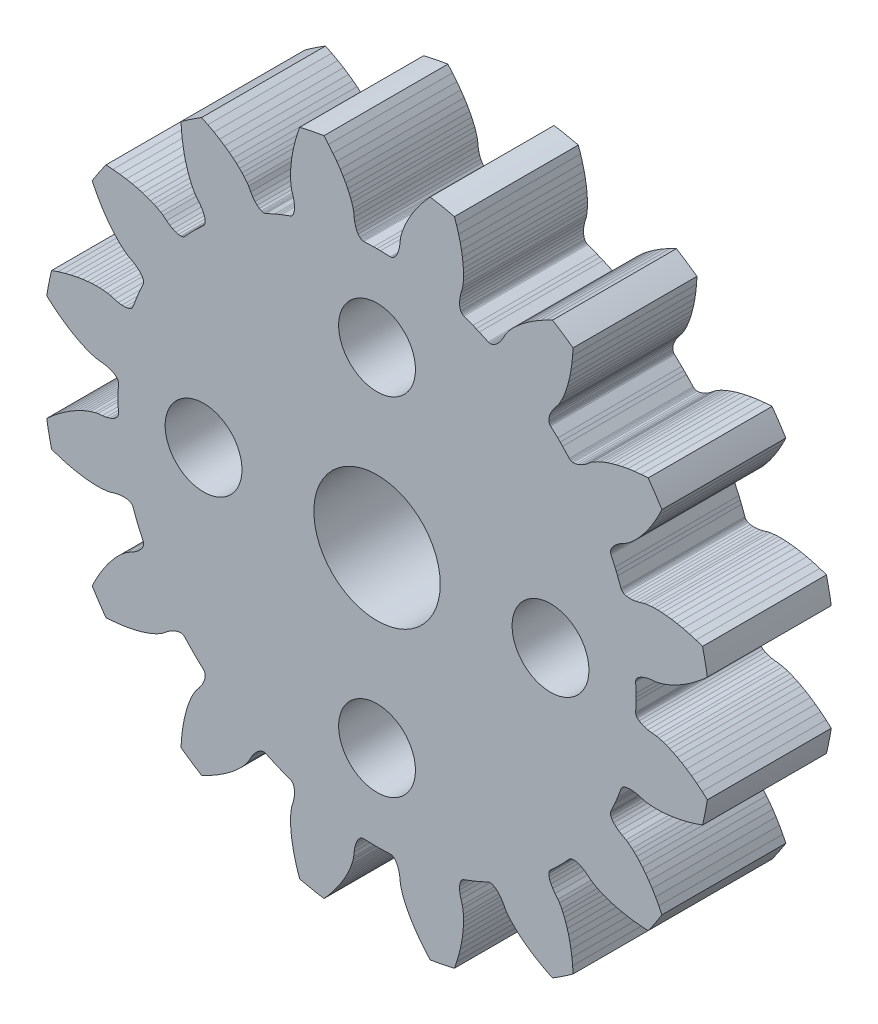
SolidWorks part; units mm, degrees
ref_plane "Płaszczyzna przednia" through (0, 0, 0) normal (0, 0, 1) x (1, 0, 0)
ref_plane "Płaszczyzna górna" through (0, 0, 0) normal (0, 1, 0) x (1, 0, 0)
ref_plane "Płaszczyzna prawa" through (0, 0, 0) normal (1, 0, 0) x (0, 0, -1)
sketch "szkic" plane through (0, 0, 0) normal (0, 0, 1) x (1, 0, 0)
  line L0 (-11.3707, -6.8275) -> (-11.2363, -6.5793)
  line L1 (-11.2363, -6.5793) -> (-11.1018, -6.3541)
  line L2 (-11.1018, -6.3541) -> (-10.9682, -6.1502)
  line L3 (-10.9682, -6.1502) -> (-10.8384, -5.969)
  line L4 (-10.8384, -5.969) -> (-10.7123, -5.8079)
  line L5 (-10.7123, -5.8079) -> (-10.5942, -5.6692)
  line L6 (-10.5942, -5.6692) -> (-10.4825, -5.5487)
  line L7 (-10.4825, -5.5487) -> (-10.3808, -5.4477)
  line L8 (-10.3808, -5.4477) -> (-10.2894, -5.3643)
  line L9 (-10.2894, -5.3643) -> (-10.1409, -5.2443)
  line L10 (-10.1409, -5.2443) -> (-10.0492, -5.182)
  line L11 (-10.0492, -5.182) -> (-9.889, -5.098)
  line L12 (-9.889, -5.098) -> (-9.7507, -5.012)
  line L13 (-9.7507, -5.012) -> (-9.6368, -4.9243)
  line L14 (-9.6368, -4.9243) -> (-9.5471, -4.8366)
  line L15 (-9.5471, -4.8366) -> (-9.4815, -4.751)
  line L16 (-9.4815, -4.751) -> (-9.4395, -4.6692)
  line L17 (-9.4395, -4.6692) -> (-9.4273, -4.6302)
  line L18 (-9.4273, -4.6302) -> (-9.4208, -4.593)
  line L19 (-9.4208, -4.593) -> (-9.4199, -4.5576)
  line L20 (-9.4199, -4.5576) -> (-9.4246, -4.5243)
  line L21 (-9.4246, -4.5243) -> (-9.4382, -4.4859)
  line L22 (-9.4382, -4.4859) -> (-9.6012, -4.1255)
  line L23 (-9.6012, -4.1255) -> (-9.6545, -3.999)
  line L24 (-9.6545, -3.999) -> (-9.7063, -3.8719)
  line L25 (-9.7063, -3.8719) -> (-9.8458, -3.5018)
  line L26 (-9.8458, -3.5018) -> (-9.8633, -3.4651)
  line L27 (-9.8633, -3.4651) -> (-9.8836, -3.4382)
  line L28 (-9.8836, -3.4382) -> (-9.9092, -3.4137)
  line L29 (-9.9092, -3.4137) -> (-9.9402, -3.392)
  line L30 (-9.9402, -3.392) -> (-9.9763, -3.3732)
  line L31 (-9.9763, -3.3732) -> (-10.0639, -3.345)
  line L32 (-10.0639, -3.345) -> (-10.1708, -3.3308)
  line L33 (-10.1708, -3.3308) -> (-10.2962, -3.3322)
  line L34 (-10.2962, -3.3322) -> (-10.4388, -3.3508)
  line L35 (-10.4388, -3.3508) -> (-10.5974, -3.3878)
  line L36 (-10.5974, -3.3878) -> (-10.7701, -3.4416)
  line L37 (-10.7701, -3.4416) -> (-10.879, -3.4624)
  line L38 (-10.879, -3.4624) -> (-11.0688, -3.4826)
  line L39 (-11.0688, -3.4826) -> (-11.1924, -3.4882)
  line L40 (-11.1924, -3.4882) -> (-11.3358, -3.4887)
  line L41 (-11.3358, -3.4887) -> (-11.4999, -3.4825)
  line L42 (-11.4999, -3.4825) -> (-11.6816, -3.468)
  line L43 (-11.6816, -3.468) -> (-11.8846, -3.4432)
  line L44 (-11.8846, -3.4432) -> (-12.1046, -3.4069)
  line L45 (-12.1046, -3.4069) -> (-12.3432, -3.3572)
  line L46 (-12.3432, -3.3572) -> (-12.5975, -3.293)
  line L47 (-12.5975, -3.293) -> (-12.868, -3.2125)
  line L48 (-12.868, -3.2125) -> (-13.1342, -3.1213)
  line L49 (-13.3289, -2.1426) -> (-13.1179, -1.9564)
  line L50 (-13.1179, -1.9564) -> (-12.8987, -1.7785)
  line L51 (-12.8987, -1.7785) -> (-12.6884, -1.6219)
  line L52 (-12.6884, -1.6219) -> (-12.4869, -1.4847)
  line L53 (-12.4869, -1.4847) -> (-12.2976, -1.367)
  line L54 (-12.2976, -1.367) -> (-12.1195, -1.2664)
  line L55 (-12.1195, -1.2664) -> (-11.9572, -1.1834)
  line L56 (-11.9572, -1.1834) -> (-11.808, -1.1149)
  line L57 (-11.808, -1.1149) -> (-11.6753, -1.0605)
  line L58 (-11.6753, -1.0605) -> (-11.5589, -1.0184)
  line L59 (-11.5589, -1.0184) -> (-11.3759, -0.9644)
  line L60 (-11.3759, -0.9644) -> (-11.2673, -0.9419)
  line L61 (-11.2673, -0.9419) -> (-11.0872, -0.9256)
  line L62 (-11.0872, -0.9256) -> (-10.9265, -0.8991)
  line L63 (-10.9265, -0.8991) -> (-10.7876, -0.8616)
  line L64 (-10.7876, -0.8616) -> (-10.6713, -0.8149)
  line L65 (-10.6713, -0.8149) -> (-10.5779, -0.7609)
  line L66 (-10.5779, -0.7609) -> (-10.5078, -0.7014)
  line L67 (-10.5078, -0.7014) -> (-10.4816, -0.6701)
  line L68 (-10.4816, -0.6701) -> (-10.4613, -0.6382)
  line L69 (-10.4613, -0.6382) -> (-10.447, -0.6058)
  line L70 (-10.447, -0.6058) -> (-10.4386, -0.5732)
  line L71 (-10.4386, -0.5732) -> (-10.4364, -0.5326)
  line L72 (-10.4364, -0.5326) -> (-10.4491, -0.1373)
  line L73 (-10.4491, -0.1373) -> (-10.45, 0)
  line L74 (-10.45, 0) -> (-10.4491, 0.1373)
  line L75 (-10.4491, 0.1373) -> (-10.4364, 0.5326)
  line L76 (-10.4364, 0.5326) -> (-10.4386, 0.5732)
  line L77 (-10.4386, 0.5732) -> (-10.447, 0.6058)
  line L78 (-10.447, 0.6058) -> (-10.4613, 0.6382)
  line L79 (-10.4613, 0.6382) -> (-10.4816, 0.6701)
  line L80 (-10.4816, 0.6701) -> (-10.5078, 0.7014)
  line L81 (-10.5078, 0.7014) -> (-10.5779, 0.7609)
  line L82 (-10.5779, 0.7609) -> (-10.6713, 0.8149)
  line L83 (-10.6713, 0.8149) -> (-10.7876, 0.8616)
  line L84 (-10.7876, 0.8616) -> (-10.9265, 0.8991)
  line L85 (-10.9265, 0.8991) -> (-11.0872, 0.9256)
  line L86 (-11.0872, 0.9256) -> (-11.2673, 0.9419)
  line L87 (-11.2673, 0.9419) -> (-11.3759, 0.9644)
  line L88 (-11.3759, 0.9644) -> (-11.5589, 1.0184)
  line L89 (-11.5589, 1.0184) -> (-11.6753, 1.0605)
  line L90 (-11.6753, 1.0605) -> (-11.808, 1.1149)
  line L91 (-11.808, 1.1149) -> (-11.9572, 1.1834)
  line L92 (-11.9572, 1.1834) -> (-12.1195, 1.2663)
  line L93 (-12.1195, 1.2663) -> (-12.2976, 1.367)
  line L94 (-12.2976, 1.367) -> (-12.4869, 1.4847)
  line L95 (-12.4869, 1.4847) -> (-12.6884, 1.6219)
  line L96 (-12.6884, 1.6219) -> (-12.8987, 1.7785)
  line L97 (-12.8987, 1.7785) -> (-13.1179, 1.9564)
  line L98 (-13.1179, 1.9564) -> (-13.3289, 2.1426)
  line L99 (-13.1342, 3.1213) -> (-12.868, 3.2125)
  line L100 (-12.868, 3.2125) -> (-12.5975, 3.293)
  line L101 (-12.5975, 3.293) -> (-12.3432, 3.3572)
  line L102 (-12.3432, 3.3572) -> (-12.1046, 3.4069)
  line L103 (-12.1046, 3.4069) -> (-11.8846, 3.4432)
  line L104 (-11.8846, 3.4432) -> (-11.6816, 3.468)
  line L105 (-11.6816, 3.468) -> (-11.4999, 3.4825)
  line L106 (-11.4999, 3.4825) -> (-11.3358, 3.4887)
  line L107 (-11.3358, 3.4887) -> (-11.1924, 3.4882)
  line L108 (-11.1924, 3.4882) -> (-11.0688, 3.4826)
  line L109 (-11.0688, 3.4826) -> (-10.879, 3.4624)
  line L110 (-10.879, 3.4624) -> (-10.7701, 3.4416)
  line L111 (-10.7701, 3.4416) -> (-10.5974, 3.3878)
  line L112 (-10.5974, 3.3878) -> (-10.4388, 3.3508)
  line L113 (-10.4388, 3.3508) -> (-10.2962, 3.3322)
  line L114 (-10.2962, 3.3322) -> (-10.1708, 3.3308)
  line L115 (-10.1708, 3.3308) -> (-10.0639, 3.345)
  line L116 (-10.0639, 3.345) -> (-9.9764, 3.3732)
  line L117 (-9.9764, 3.3732) -> (-9.9402, 3.392)
  line L118 (-9.9402, 3.392) -> (-9.9092, 3.4137)
  line L119 (-9.9092, 3.4137) -> (-9.8836, 3.4382)
  line L120 (-9.8836, 3.4382) -> (-9.8633, 3.4651)
  line L121 (-9.8633, 3.4651) -> (-9.8458, 3.5018)
  line L122 (-9.8458, 3.5018) -> (-9.7063, 3.8719)
  line L123 (-9.7063, 3.8719) -> (-9.6545, 3.999)
  line L124 (-9.6545, 3.999) -> (-9.6012, 4.1255)
  line L125 (-9.6012, 4.1255) -> (-9.4382, 4.4859)
  line L126 (-9.4382, 4.4859) -> (-9.4246, 4.5243)
  line L127 (-9.4246, 4.5243) -> (-9.4199, 4.5576)
  line L128 (-9.4199, 4.5576) -> (-9.4208, 4.593)
  line L129 (-9.4208, 4.593) -> (-9.4273, 4.6303)
  line L130 (-9.4273, 4.6303) -> (-9.4395, 4.6692)
  line L131 (-9.4395, 4.6692) -> (-9.4815, 4.751)
  line L132 (-9.4815, 4.751) -> (-9.5471, 4.8366)
  line L133 (-9.5471, 4.8366) -> (-9.6368, 4.9243)
  line L134 (-9.6368, 4.9243) -> (-9.7507, 5.012)
  line L135 (-9.7507, 5.012) -> (-9.889, 5.098)
  line L136 (-9.889, 5.098) -> (-10.0492, 5.182)
  line L137 (-10.0492, 5.182) -> (-10.1409, 5.2443)
  line L138 (-10.1409, 5.2443) -> (-10.2894, 5.3643)
  line L139 (-10.2894, 5.3643) -> (-10.3808, 5.4477)
  line L140 (-10.3808, 5.4477) -> (-10.4825, 5.5487)
  line L141 (-10.4825, 5.5487) -> (-10.5942, 5.6692)
  line L142 (-10.5942, 5.6692) -> (-10.7123, 5.8079)
  line L143 (-10.7123, 5.8079) -> (-10.8384, 5.969)
  line L144 (-10.8384, 5.969) -> (-10.9683, 6.1502)
  line L145 (-10.9683, 6.1502) -> (-11.1018, 6.3541)
  line L146 (-11.1018, 6.3541) -> (-11.2363, 6.5793)
  line L147 (-11.2363, 6.5793) -> (-11.3707, 6.8275)
  line L148 (-11.3707, 6.8275) -> (-11.4943, 7.0802)
  line L149 (-10.9399, 7.9099) -> (-10.6591, 7.8924)
  line L150 (-10.6591, 7.8924) -> (-10.3784, 7.8632)
  line L151 (-10.3784, 7.8632) -> (-10.1189, 7.8252)
  line L152 (-10.1189, 7.8252) -> (-9.8794, 7.7798)
  line L153 (-9.8794, 7.7798) -> (-9.6623, 7.7291)
  line L154 (-9.6623, 7.7291) -> (-9.4652, 7.6743)
  line L155 (-9.4652, 7.6743) -> (-9.2919, 7.6182)
  line L156 (-9.2919, 7.6182) -> (-9.1378, 7.5612)
  line L157 (-9.1378, 7.5612) -> (-9.0056, 7.5058)
  line L158 (-9.0056, 7.5058) -> (-8.8935, 7.4533)
  line L159 (-8.8935, 7.4533) -> (-8.7259, 7.362)
  line L160 (-8.7259, 7.362) -> (-8.6332, 7.3012)
  line L161 (-8.6332, 7.3012) -> (-8.4943, 7.1854)
  line L162 (-8.4943, 7.1854) -> (-8.3619, 7.0905)
  line L163 (-8.3619, 7.0905) -> (-8.2373, 7.0188)
  line L164 (-8.2373, 7.0188) -> (-8.122, 6.9695)
  line L165 (-8.122, 6.9695) -> (-8.0177, 6.9416)
  line L166 (-8.0177, 6.9416) -> (-7.9261, 6.9342)
  line L167 (-7.9261, 6.9342) -> (-7.8855, 6.9378)
  line L168 (-7.8855, 6.9378) -> (-7.8485, 6.946)
  line L169 (-7.8485, 6.946) -> (-7.8155, 6.9587)
  line L170 (-7.8155, 6.9587) -> (-7.7865, 6.9758)
  line L171 (-7.7865, 6.9758) -> (-7.7562, 7.0031)
  line L172 (-7.7562, 7.0031) -> (-7.4857, 7.2916)
  line L173 (-7.4857, 7.2916) -> (-7.3893, 7.3893)
  line L174 (-7.3893, 7.3893) -> (-7.2916, 7.4857)
  line L175 (-7.2916, 7.4857) -> (-7.0031, 7.7562)
  line L176 (-7.0031, 7.7562) -> (-6.9758, 7.7865)
  line L177 (-6.9758, 7.7865) -> (-6.9587, 7.8155)
  line L178 (-6.9587, 7.8155) -> (-6.946, 7.8485)
  line L179 (-6.946, 7.8485) -> (-6.9378, 7.8855)
  line L180 (-6.9378, 7.8855) -> (-6.9342, 7.9261)
  line L181 (-6.9342, 7.9261) -> (-6.9416, 8.0177)
  line L182 (-6.9416, 8.0177) -> (-6.9695, 8.122)
  line L183 (-6.9695, 8.122) -> (-7.0188, 8.2373)
  line L184 (-7.0188, 8.2373) -> (-7.0905, 8.3619)
  line L185 (-7.0905, 8.3619) -> (-7.1854, 8.4943)
  line L186 (-7.1854, 8.4943) -> (-7.3012, 8.6332)
  line L187 (-7.3012, 8.6332) -> (-7.362, 8.7259)
  line L188 (-7.362, 8.7259) -> (-7.4533, 8.8935)
  line L189 (-7.4533, 8.8935) -> (-7.5058, 9.0056)
  line L190 (-7.5058, 9.0056) -> (-7.5612, 9.1378)
  line L191 (-7.5612, 9.1378) -> (-7.6182, 9.2919)
  line L192 (-7.6182, 9.2919) -> (-7.6743, 9.4652)
  line L193 (-7.6743, 9.4652) -> (-7.7291, 9.6623)
  line L194 (-7.7291, 9.6623) -> (-7.7798, 9.8794)
  line L195 (-7.7798, 9.8794) -> (-7.8252, 10.1189)
  line L196 (-7.8252, 10.1189) -> (-7.8632, 10.3784)
  line L197 (-7.8632, 10.3784) -> (-7.8924, 10.6591)
  line L198 (-7.8924, 10.6591) -> (-7.9099, 10.9399)
  line L199 (-7.0802, 11.4943) -> (-6.8275, 11.3707)
  line L200 (-6.8275, 11.3707) -> (-6.5793, 11.2363)
  line L201 (-6.5793, 11.2363) -> (-6.3541, 11.1018)
  line L202 (-6.3541, 11.1018) -> (-6.1502, 10.9683)
  line L203 (-6.1502, 10.9683) -> (-5.969, 10.8384)
  line L204 (-5.969, 10.8384) -> (-5.8079, 10.7123)
  line L205 (-5.8079, 10.7123) -> (-5.6692, 10.5942)
  line L206 (-5.6692, 10.5942) -> (-5.5487, 10.4825)
  line L207 (-5.5487, 10.4825) -> (-5.4477, 10.3808)
  line L208 (-5.4477, 10.3808) -> (-5.3643, 10.2894)
  line L209 (-5.3643, 10.2894) -> (-5.2443, 10.1409)
  line L210 (-5.2443, 10.1409) -> (-5.182, 10.0492)
  line L211 (-5.182, 10.0492) -> (-5.098, 9.889)
  line L212 (-5.098, 9.889) -> (-5.012, 9.7507)
  line L213 (-5.012, 9.7507) -> (-4.9243, 9.6368)
  line L214 (-4.9243, 9.6368) -> (-4.8366, 9.5471)
  line L215 (-4.8366, 9.5471) -> (-4.751, 9.4815)
  line L216 (-4.751, 9.4815) -> (-4.6692, 9.4395)
  line L217 (-4.6692, 9.4395) -> (-4.6303, 9.4273)
  line L218 (-4.6303, 9.4273) -> (-4.593, 9.4208)
  line L219 (-4.593, 9.4208) -> (-4.5576, 9.4199)
  line L220 (-4.5576, 9.4199) -> (-4.5243, 9.4246)
  line L221 (-4.5243, 9.4246) -> (-4.4859, 9.4382)
  line L222 (-4.4859, 9.4382) -> (-4.1255, 9.6012)
  line L223 (-4.1255, 9.6012) -> (-3.999, 9.6545)
  line L224 (-3.999, 9.6545) -> (-3.8719, 9.7063)
  line L225 (-3.8719, 9.7063) -> (-3.5018, 9.8458)
  line L226 (-3.5018, 9.8458) -> (-3.4651, 9.8633)
  line L227 (-3.4651, 9.8633) -> (-3.4382, 9.8836)
  line L228 (-3.4382, 9.8836) -> (-3.4137, 9.9092)
  line L229 (-3.4137, 9.9092) -> (-3.392, 9.9402)
  line L230 (-3.392, 9.9402) -> (-3.3732, 9.9764)
  line L231 (-3.3732, 9.9764) -> (-3.345, 10.0639)
  line L232 (-3.345, 10.0639) -> (-3.3308, 10.1709)
  line L233 (-3.3308, 10.1709) -> (-3.3322, 10.2962)
  line L234 (-3.3322, 10.2962) -> (-3.3508, 10.4388)
  line L235 (-3.3508, 10.4388) -> (-3.3878, 10.5974)
  line L236 (-3.3878, 10.5974) -> (-3.4416, 10.7701)
  line L237 (-3.4416, 10.7701) -> (-3.4624, 10.879)
  line L238 (-3.4624, 10.879) -> (-3.4826, 11.0688)
  line L239 (-3.4826, 11.0688) -> (-3.4882, 11.1924)
  line L240 (-3.4882, 11.1924) -> (-3.4887, 11.3358)
  line L241 (-3.4887, 11.3358) -> (-3.4825, 11.4999)
  line L242 (-3.4825, 11.4999) -> (-3.468, 11.6816)
  line L243 (-3.468, 11.6816) -> (-3.4432, 11.8846)
  line L244 (-3.4432, 11.8846) -> (-3.4069, 12.1046)
  line L245 (-3.4069, 12.1046) -> (-3.3572, 12.3432)
  line L246 (-3.3572, 12.3432) -> (-3.293, 12.5975)
  line L247 (-3.293, 12.5975) -> (-3.2125, 12.868)
  line L248 (-3.2125, 12.868) -> (-3.1213, 13.1342)
  line L249 (-2.1426, 13.3289) -> (-1.9564, 13.1179)
  line L250 (-1.9564, 13.1179) -> (-1.7785, 12.8987)
  line L251 (-1.7785, 12.8987) -> (-1.6219, 12.6884)
  line L252 (-1.6219, 12.6884) -> (-1.4847, 12.4869)
  line L253 (-1.4847, 12.4869) -> (-1.367, 12.2976)
  line L254 (-1.367, 12.2976) -> (-1.2663, 12.1195)
  line L255 (-1.2663, 12.1195) -> (-1.1834, 11.9572)
  line L256 (-1.1834, 11.9572) -> (-1.1149, 11.808)
  line L257 (-1.1149, 11.808) -> (-1.0605, 11.6753)
  line L258 (-1.0605, 11.6753) -> (-1.0184, 11.5589)
  line L259 (-1.0184, 11.5589) -> (-0.9644, 11.3759)
  line L260 (-0.9644, 11.3759) -> (-0.9419, 11.2673)
  line L261 (-0.9419, 11.2673) -> (-0.9256, 11.0872)
  line L262 (-0.9256, 11.0872) -> (-0.8991, 10.9265)
  line L263 (-0.8991, 10.9265) -> (-0.8616, 10.7876)
  line L264 (-0.8616, 10.7876) -> (-0.8149, 10.6713)
  line L265 (-0.8149, 10.6713) -> (-0.7609, 10.5779)
  line L266 (-0.7609, 10.5779) -> (-0.7014, 10.5078)
  line L267 (-0.7014, 10.5078) -> (-0.6701, 10.4816)
  line L268 (-0.6701, 10.4816) -> (-0.6382, 10.4613)
  line L269 (-0.6382, 10.4613) -> (-0.6058, 10.447)
  line L270 (-0.6058, 10.447) -> (-0.5732, 10.4386)
  line L271 (-0.5732, 10.4386) -> (-0.5326, 10.4364)
  line L272 (-0.5326, 10.4364) -> (-0.1373, 10.4491)
  line L273 (-0.1373, 10.4491) -> (0, 10.45)
  line L274 (0, 10.45) -> (0.1373, 10.4491)
  line L275 (0.1373, 10.4491) -> (0.5326, 10.4364)
  line L276 (0.5326, 10.4364) -> (0.5732, 10.4386)
  line L277 (0.5732, 10.4386) -> (0.6058, 10.447)
  line L278 (0.6058, 10.447) -> (0.6382, 10.4613)
  line L279 (0.6382, 10.4613) -> (0.6701, 10.4816)
  line L280 (0.6701, 10.4816) -> (0.7014, 10.5078)
  line L281 (0.7014, 10.5078) -> (0.7609, 10.5779)
  line L282 (0.7609, 10.5779) -> (0.8149, 10.6713)
  line L283 (0.8149, 10.6713) -> (0.8616, 10.7876)
  line L284 (0.8616, 10.7876) -> (0.8991, 10.9265)
  line L285 (0.8991, 10.9265) -> (0.9256, 11.0872)
  line L286 (0.9256, 11.0872) -> (0.9419, 11.2673)
  line L287 (0.9419, 11.2673) -> (0.9644, 11.3759)
  line L288 (0.9644, 11.3759) -> (1.0184, 11.5589)
  line L289 (1.0184, 11.5589) -> (1.0605, 11.6753)
  line L290 (1.0605, 11.6753) -> (1.1149, 11.808)
  line L291 (1.1149, 11.808) -> (1.1834, 11.9572)
  line L292 (1.1834, 11.9572) -> (1.2664, 12.1195)
  line L293 (1.2664, 12.1195) -> (1.367, 12.2976)
  line L294 (1.367, 12.2976) -> (1.4847, 12.4869)
  line L295 (1.4847, 12.4869) -> (1.6219, 12.6884)
  line L296 (1.6219, 12.6884) -> (1.7785, 12.8987)
  line L297 (1.7785, 12.8987) -> (1.9564, 13.1179)
  line L298 (1.9564, 13.1179) -> (2.1426, 13.3289)
  line L299 (3.1213, 13.1342) -> (3.2125, 12.868)
  line L300 (3.2125, 12.868) -> (3.293, 12.5975)
  line L301 (3.293, 12.5975) -> (3.3572, 12.3432)
  line L302 (3.3572, 12.3432) -> (3.4069, 12.1046)
  line L303 (3.4069, 12.1046) -> (3.4432, 11.8846)
  line L304 (3.4432, 11.8846) -> (3.468, 11.6816)
  line L305 (3.468, 11.6816) -> (3.4825, 11.4999)
  line L306 (3.4825, 11.4999) -> (3.4887, 11.3358)
  line L307 (3.4887, 11.3358) -> (3.4882, 11.1924)
  line L308 (3.4882, 11.1924) -> (3.4826, 11.0688)
  line L309 (3.4826, 11.0688) -> (3.4624, 10.879)
  line L310 (3.4624, 10.879) -> (3.4416, 10.7701)
  line L311 (3.4416, 10.7701) -> (3.3878, 10.5974)
  line L312 (3.3878, 10.5974) -> (3.3508, 10.4388)
  line L313 (3.3508, 10.4388) -> (3.3322, 10.2962)
  line L314 (3.3322, 10.2962) -> (3.3308, 10.1709)
  line L315 (3.3308, 10.1709) -> (3.345, 10.0639)
  line L316 (3.345, 10.0639) -> (3.3732, 9.9764)
  line L317 (3.3732, 9.9764) -> (3.392, 9.9402)
  line L318 (3.392, 9.9402) -> (3.4138, 9.9092)
  line L319 (3.4138, 9.9092) -> (3.4382, 9.8836)
  line L320 (3.4382, 9.8836) -> (3.4651, 9.8633)
  line L321 (3.4651, 9.8633) -> (3.5018, 9.8458)
  line L322 (3.5018, 9.8458) -> (3.8719, 9.7063)
  line L323 (3.8719, 9.7063) -> (3.999, 9.6545)
  line L324 (3.999, 9.6545) -> (4.1255, 9.6012)
  line L325 (4.1255, 9.6012) -> (4.4859, 9.4382)
  line L326 (4.4859, 9.4382) -> (4.5243, 9.4246)
  line L327 (4.5243, 9.4246) -> (4.5576, 9.4199)
  line L328 (4.5576, 9.4199) -> (4.593, 9.4208)
  line L329 (4.593, 9.4208) -> (4.6303, 9.4273)
  line L330 (4.6303, 9.4273) -> (4.6692, 9.4395)
  line L331 (4.6692, 9.4395) -> (4.751, 9.4815)
  line L332 (4.751, 9.4815) -> (4.8366, 9.5471)
  line L333 (4.8366, 9.5471) -> (4.9243, 9.6368)
  line L334 (4.9243, 9.6368) -> (5.012, 9.7507)
  line L335 (5.012, 9.7507) -> (5.098, 9.889)
  line L336 (5.098, 9.889) -> (5.182, 10.0492)
  line L337 (5.182, 10.0492) -> (5.2443, 10.1409)
  line L338 (5.2443, 10.1409) -> (5.3643, 10.2894)
  line L339 (5.3643, 10.2894) -> (5.4477, 10.3808)
  line L340 (5.4477, 10.3808) -> (5.5487, 10.4825)
  line L341 (5.5487, 10.4825) -> (5.6692, 10.5942)
  line L342 (5.6692, 10.5942) -> (5.8079, 10.7123)
  line L343 (5.8079, 10.7123) -> (5.969, 10.8384)
  line L344 (5.969, 10.8384) -> (6.1502, 10.9683)
  line L345 (6.1502, 10.9683) -> (6.3541, 11.1018)
  line L346 (6.3541, 11.1018) -> (6.5793, 11.2363)
  line L347 (6.5793, 11.2363) -> (6.8275, 11.3707)
  line L348 (6.8275, 11.3707) -> (7.0802, 11.4943)
  line L349 (7.9099, 10.9399) -> (7.8924, 10.6591)
  line L350 (7.8924, 10.6591) -> (7.8632, 10.3784)
  line L351 (7.8632, 10.3784) -> (7.8252, 10.1189)
  line L352 (7.8252, 10.1189) -> (7.7798, 9.8794)
  line L353 (7.7798, 9.8794) -> (7.7291, 9.6623)
  line L354 (7.7291, 9.6623) -> (7.6743, 9.4652)
  line L355 (7.6743, 9.4652) -> (7.6182, 9.2919)
  line L356 (7.6182, 9.2919) -> (7.5612, 9.1378)
  line L357 (7.5612, 9.1378) -> (7.5058, 9.0056)
  line L358 (7.5058, 9.0056) -> (7.4533, 8.8935)
  line L359 (7.4533, 8.8935) -> (7.362, 8.7259)
  line L360 (7.362, 8.7259) -> (7.3012, 8.6332)
  line L361 (7.3012, 8.6332) -> (7.1854, 8.4943)
  line L362 (7.1854, 8.4943) -> (7.0905, 8.3619)
  line L363 (7.0905, 8.3619) -> (7.0188, 8.2373)
  line L364 (7.0188, 8.2373) -> (6.9695, 8.122)
  line L365 (6.9695, 8.122) -> (6.9416, 8.0177)
  line L366 (6.9416, 8.0177) -> (6.9342, 7.9261)
  line L367 (6.9342, 7.9261) -> (6.9378, 7.8855)
  line L368 (6.9378, 7.8855) -> (6.946, 7.8485)
  line L369 (6.946, 7.8485) -> (6.9587, 7.8155)
  line L370 (6.9587, 7.8155) -> (6.9758, 7.7865)
  line L371 (6.9758, 7.7865) -> (7.0031, 7.7562)
  line L372 (7.0031, 7.7562) -> (7.2916, 7.4857)
  line L373 (7.2916, 7.4857) -> (7.3893, 7.3893)
  line L374 (7.3893, 7.3893) -> (7.4857, 7.2916)
  line L375 (7.4857, 7.2916) -> (7.7562, 7.0031)
  line L376 (7.7562, 7.0031) -> (7.7865, 6.9758)
  line L377 (7.7865, 6.9758) -> (7.8155, 6.9587)
  line L378 (7.8155, 6.9587) -> (7.8485, 6.946)
  line L379 (7.8485, 6.946) -> (7.8855, 6.9378)
  line L380 (7.8855, 6.9378) -> (7.9261, 6.9342)
  line L381 (7.9261, 6.9342) -> (8.0177, 6.9416)
  line L382 (8.0177, 6.9416) -> (8.122, 6.9695)
  line L383 (8.122, 6.9695) -> (8.2373, 7.0188)
  line L384 (8.2373, 7.0188) -> (8.3619, 7.0905)
  line L385 (8.3619, 7.0905) -> (8.4943, 7.1854)
  line L386 (8.4943, 7.1854) -> (8.6332, 7.3012)
  line L387 (8.6332, 7.3012) -> (8.7259, 7.362)
  line L388 (8.7259, 7.362) -> (8.8935, 7.4533)
  line L389 (8.8935, 7.4533) -> (9.0056, 7.5058)
  line L390 (9.0056, 7.5058) -> (9.1378, 7.5612)
  line L391 (9.1378, 7.5612) -> (9.2919, 7.6182)
  line L392 (9.2919, 7.6182) -> (9.4652, 7.6743)
  line L393 (9.4652, 7.6743) -> (9.6623, 7.7291)
  line L394 (9.6623, 7.7291) -> (9.8794, 7.7798)
  line L395 (9.8794, 7.7798) -> (10.1189, 7.8252)
  line L396 (10.1189, 7.8252) -> (10.3784, 7.8632)
  line L397 (10.3784, 7.8632) -> (10.6591, 7.8924)
  line L398 (10.6591, 7.8924) -> (10.9399, 7.9099)
  line L399 (11.4943, 7.0802) -> (11.3707, 6.8275)
  line L400 (11.3707, 6.8275) -> (11.2363, 6.5793)
  line L401 (11.2363, 6.5793) -> (11.1018, 6.3541)
  line L402 (11.1018, 6.3541) -> (10.9683, 6.1502)
  line L403 (10.9683, 6.1502) -> (10.8384, 5.969)
  line L404 (10.8384, 5.969) -> (10.7123, 5.8079)
  line L405 (10.7123, 5.8079) -> (10.5942, 5.6692)
  line L406 (10.5942, 5.6692) -> (10.4825, 5.5487)
  line L407 (10.4825, 5.5487) -> (10.3808, 5.4477)
  line L408 (10.3808, 5.4477) -> (10.2894, 5.3643)
  line L409 (10.2894, 5.3643) -> (10.1409, 5.2443)
  line L410 (10.1409, 5.2443) -> (10.0492, 5.182)
  line L411 (10.0492, 5.182) -> (9.889, 5.098)
  line L412 (9.889, 5.098) -> (9.7507, 5.012)
  line L413 (9.7507, 5.012) -> (9.6368, 4.9243)
  line L414 (9.6368, 4.9243) -> (9.5471, 4.8366)
  line L415 (9.5471, 4.8366) -> (9.4815, 4.751)
  line L416 (9.4815, 4.751) -> (9.4395, 4.6692)
  line L417 (9.4395, 4.6692) -> (9.4273, 4.6303)
  line L418 (9.4273, 4.6303) -> (9.4208, 4.593)
  line L419 (9.4208, 4.593) -> (9.4199, 4.5576)
  line L420 (9.4199, 4.5576) -> (9.4246, 4.5243)
  line L421 (9.4246, 4.5243) -> (9.4382, 4.4859)
  line L422 (9.4382, 4.4859) -> (9.6012, 4.1255)
  line L423 (9.6012, 4.1255) -> (9.6545, 3.999)
  line L424 (9.6545, 3.999) -> (9.7063, 3.8719)
  line L425 (9.7063, 3.8719) -> (9.8458, 3.5018)
  line L426 (9.8458, 3.5018) -> (9.8633, 3.4651)
  line L427 (9.8633, 3.4651) -> (9.8836, 3.4382)
  line L428 (9.8836, 3.4382) -> (9.9092, 3.4138)
  line L429 (9.9092, 3.4138) -> (9.9402, 3.392)
  line L430 (9.9402, 3.392) -> (9.9764, 3.3732)
  line L431 (9.9764, 3.3732) -> (10.0639, 3.345)
  line L432 (10.0639, 3.345) -> (10.1709, 3.3308)
  line L433 (10.1709, 3.3308) -> (10.2962, 3.3323)
  line L434 (10.2962, 3.3323) -> (10.4388, 3.3508)
  line L435 (10.4388, 3.3508) -> (10.5974, 3.3878)
  line L436 (10.5974, 3.3878) -> (10.7701, 3.4416)
  line L437 (10.7701, 3.4416) -> (10.879, 3.4624)
  line L438 (10.879, 3.4624) -> (11.0688, 3.4826)
  line L439 (11.0688, 3.4826) -> (11.1924, 3.4882)
  line L440 (11.1924, 3.4882) -> (11.3358, 3.4887)
  line L441 (11.3358, 3.4887) -> (11.4999, 3.4825)
  line L442 (11.4999, 3.4825) -> (11.6816, 3.468)
  line L443 (11.6816, 3.468) -> (11.8846, 3.4432)
  line L444 (11.8846, 3.4432) -> (12.1046, 3.4069)
  line L445 (12.1046, 3.4069) -> (12.3432, 3.3572)
  line L446 (12.3432, 3.3572) -> (12.5975, 3.293)
  line L447 (12.5975, 3.293) -> (12.868, 3.2125)
  line L448 (12.868, 3.2125) -> (13.1342, 3.1213)
  line L449 (13.3289, 2.1426) -> (13.1179, 1.9564)
  line L450 (13.1179, 1.9564) -> (12.8988, 1.7785)
  line L451 (12.8988, 1.7785) -> (12.6884, 1.6219)
  line L452 (12.6884, 1.6219) -> (12.4869, 1.4847)
  line L453 (12.4869, 1.4847) -> (12.2976, 1.367)
  line L454 (12.2976, 1.367) -> (12.1195, 1.2664)
  line L455 (12.1195, 1.2664) -> (11.9573, 1.1834)
  line L456 (11.9573, 1.1834) -> (11.808, 1.1149)
  line L457 (11.808, 1.1149) -> (11.6753, 1.0605)
  line L458 (11.6753, 1.0605) -> (11.5589, 1.0184)
  line L459 (11.5589, 1.0184) -> (11.3759, 0.9644)
  line L460 (11.3759, 0.9644) -> (11.2673, 0.9419)
  line L461 (11.2673, 0.9419) -> (11.0872, 0.9256)
  line L462 (11.0872, 0.9256) -> (10.9265, 0.8991)
  line L463 (10.9265, 0.8991) -> (10.7877, 0.8616)
  line L464 (10.7877, 0.8616) -> (10.6713, 0.8149)
  line L465 (10.6713, 0.8149) -> (10.5779, 0.7609)
  line L466 (10.5779, 0.7609) -> (10.5078, 0.7014)
  line L467 (10.5078, 0.7014) -> (10.4816, 0.6701)
  line L468 (10.4816, 0.6701) -> (10.4613, 0.6382)
  line L469 (10.4613, 0.6382) -> (10.447, 0.6058)
  line L470 (10.447, 0.6058) -> (10.4386, 0.5732)
  line L471 (10.4386, 0.5732) -> (10.4364, 0.5326)
  line L472 (10.4364, 0.5326) -> (10.4491, 0.1373)
  line L473 (10.4491, 0.1373) -> (10.45, 0)
  line L474 (10.45, 0) -> (10.4491, -0.1373)
  line L475 (10.4491, -0.1373) -> (10.4364, -0.5326)
  line L476 (10.4364, -0.5326) -> (10.4386, -0.5732)
  line L477 (10.4386, -0.5732) -> (10.447, -0.6058)
  line L478 (10.447, -0.6058) -> (10.4613, -0.6382)
  line L479 (10.4613, -0.6382) -> (10.4816, -0.6701)
  line L480 (10.4816, -0.6701) -> (10.5078, -0.7014)
  line L481 (10.5078, -0.7014) -> (10.5779, -0.7609)
  line L482 (10.5779, -0.7609) -> (10.6713, -0.8149)
  line L483 (10.6713, -0.8149) -> (10.7877, -0.8616)
  line L484 (10.7877, -0.8616) -> (10.9265, -0.8991)
  line L485 (10.9265, -0.8991) -> (11.0872, -0.9256)
  line L486 (11.0872, -0.9256) -> (11.2673, -0.9419)
  line L487 (11.2673, -0.9419) -> (11.3759, -0.9644)
  line L488 (11.3759, -0.9644) -> (11.5589, -1.0184)
  line L489 (11.5589, -1.0184) -> (11.6753, -1.0605)
  line L490 (11.6753, -1.0605) -> (11.808, -1.1149)
  line L491 (11.808, -1.1149) -> (11.9573, -1.1834)
  line L492 (11.9573, -1.1834) -> (12.1195, -1.2663)
  line L493 (12.1195, -1.2663) -> (12.2976, -1.367)
  line L494 (12.2976, -1.367) -> (12.4869, -1.4847)
  line L495 (12.4869, -1.4847) -> (12.6884, -1.6219)
  line L496 (12.6884, -1.6219) -> (12.8988, -1.7785)
  line L497 (12.8988, -1.7785) -> (13.1179, -1.9564)
  line L498 (13.1179, -1.9564) -> (13.3289, -2.1426)
  line L499 (13.1342, -3.1213) -> (12.868, -3.2125)
  line L500 (12.868, -3.2125) -> (12.5975, -3.293)
  line L501 (12.5975, -3.293) -> (12.3432, -3.3572)
  line L502 (12.3432, -3.3572) -> (12.1046, -3.4069)
  line L503 (12.1046, -3.4069) -> (11.8846, -3.4432)
  line L504 (11.8846, -3.4432) -> (11.6816, -3.468)
  line L505 (11.6816, -3.468) -> (11.4999, -3.4825)
  line L506 (11.4999, -3.4825) -> (11.3358, -3.4887)
  line L507 (11.3358, -3.4887) -> (11.1924, -3.4882)
  line L508 (11.1924, -3.4882) -> (11.0688, -3.4826)
  line L509 (11.0688, -3.4826) -> (10.879, -3.4624)
  line L510 (10.879, -3.4624) -> (10.7701, -3.4416)
  line L511 (10.7701, -3.4416) -> (10.5974, -3.3878)
  line L512 (10.5974, -3.3878) -> (10.4388, -3.3508)
  line L513 (10.4388, -3.3508) -> (10.2962, -3.3322)
  line L514 (10.2962, -3.3322) -> (10.1709, -3.3308)
  line L515 (10.1709, -3.3308) -> (10.0639, -3.345)
  line L516 (10.0639, -3.345) -> (9.9764, -3.3732)
  line L517 (9.9764, -3.3732) -> (9.9402, -3.392)
  line L518 (9.9402, -3.392) -> (9.9092, -3.4137)
  line L519 (9.9092, -3.4137) -> (9.8836, -3.4382)
  line L520 (9.8836, -3.4382) -> (9.8633, -3.4651)
  line L521 (9.8633, -3.4651) -> (9.8458, -3.5018)
  line L522 (9.8458, -3.5018) -> (9.7063, -3.8719)
  line L523 (9.7063, -3.8719) -> (9.6545, -3.999)
  line L524 (9.6545, -3.999) -> (9.6012, -4.1255)
  line L525 (9.6012, -4.1255) -> (9.4382, -4.4859)
  line L526 (9.4382, -4.4859) -> (9.4246, -4.5243)
  line L527 (9.4246, -4.5243) -> (9.4199, -4.5576)
  line L528 (9.4199, -4.5576) -> (9.4208, -4.593)
  line L529 (9.4208, -4.593) -> (9.4273, -4.6303)
  line L530 (9.4273, -4.6303) -> (9.4395, -4.6692)
  line L531 (9.4395, -4.6692) -> (9.4815, -4.751)
  line L532 (9.4815, -4.751) -> (9.5471, -4.8366)
  line L533 (9.5471, -4.8366) -> (9.6368, -4.9243)
  line L534 (9.6368, -4.9243) -> (9.7507, -5.012)
  line L535 (9.7507, -5.012) -> (9.889, -5.098)
  line L536 (9.889, -5.098) -> (10.0492, -5.182)
  line L537 (10.0492, -5.182) -> (10.1409, -5.2443)
  line L538 (10.1409, -5.2443) -> (10.2894, -5.3643)
  line L539 (10.2894, -5.3643) -> (10.3808, -5.4477)
  line L540 (10.3808, -5.4477) -> (10.4825, -5.5487)
  line L541 (10.4825, -5.5487) -> (10.5942, -5.6692)
  line L542 (10.5942, -5.6692) -> (10.7123, -5.8079)
  line L543 (10.7123, -5.8079) -> (10.8384, -5.969)
  line L544 (10.8384, -5.969) -> (10.9683, -6.1502)
  line L545 (10.9683, -6.1502) -> (11.1018, -6.3541)
  line L546 (11.1018, -6.3541) -> (11.2363, -6.5793)
  line L547 (11.2363, -6.5793) -> (11.3707, -6.8275)
  line L548 (11.3707, -6.8275) -> (11.4943, -7.0802)
  line L549 (10.9399, -7.9099) -> (10.6592, -7.8924)
  line L550 (10.6592, -7.8924) -> (10.3784, -7.8632)
  line L551 (10.3784, -7.8632) -> (10.1189, -7.8252)
  line L552 (10.1189, -7.8252) -> (9.8794, -7.7798)
  line L553 (9.8794, -7.7798) -> (9.6623, -7.7291)
  line L554 (9.6623, -7.7291) -> (9.4652, -7.6743)
  line L555 (9.4652, -7.6743) -> (9.2919, -7.6182)
  line L556 (9.2919, -7.6182) -> (9.1378, -7.5612)
  line L557 (9.1378, -7.5612) -> (9.0056, -7.5058)
  line L558 (9.0056, -7.5058) -> (8.8935, -7.4533)
  line L559 (8.8935, -7.4533) -> (8.7259, -7.362)
  line L560 (8.7259, -7.362) -> (8.6332, -7.3012)
  line L561 (8.6332, -7.3012) -> (8.4943, -7.1854)
  line L562 (8.4943, -7.1854) -> (8.3619, -7.0905)
  line L563 (8.3619, -7.0905) -> (8.2373, -7.0188)
  line L564 (8.2373, -7.0188) -> (8.122, -6.9695)
  line L565 (8.122, -6.9695) -> (8.0177, -6.9416)
  line L566 (8.0177, -6.9416) -> (7.9261, -6.9342)
  line L567 (7.9261, -6.9342) -> (7.8855, -6.9378)
  line L568 (7.8855, -6.9378) -> (7.8485, -6.946)
  line L569 (7.8485, -6.946) -> (7.8155, -6.9587)
  line L570 (7.8155, -6.9587) -> (7.7865, -6.9758)
  line L571 (7.7865, -6.9758) -> (7.7563, -7.0031)
  line L572 (7.7563, -7.0031) -> (7.4857, -7.2916)
  line L573 (7.4857, -7.2916) -> (7.3893, -7.3893)
  line L574 (7.3893, -7.3893) -> (7.2916, -7.4857)
  line L575 (7.2916, -7.4857) -> (7.0031, -7.7562)
  line L576 (7.0031, -7.7562) -> (6.9759, -7.7865)
  line L577 (6.9759, -7.7865) -> (6.9587, -7.8155)
  line L578 (6.9587, -7.8155) -> (6.946, -7.8485)
  line L579 (6.946, -7.8485) -> (6.9378, -7.8855)
  line L580 (6.9378, -7.8855) -> (6.9342, -7.9261)
  line L581 (6.9342, -7.9261) -> (6.9416, -8.0177)
  line L582 (6.9416, -8.0177) -> (6.9695, -8.122)
  line L583 (6.9695, -8.122) -> (7.0188, -8.2373)
  line L584 (7.0188, -8.2373) -> (7.0905, -8.3619)
  line L585 (7.0905, -8.3619) -> (7.1854, -8.4943)
  line L586 (7.1854, -8.4943) -> (7.3012, -8.6332)
  line L587 (7.3012, -8.6332) -> (7.3621, -8.7259)
  line L588 (7.3621, -8.7259) -> (7.4533, -8.8935)
  line L589 (7.4533, -8.8935) -> (7.5058, -9.0056)
  line L590 (7.5058, -9.0056) -> (7.5612, -9.1378)
  line L591 (7.5612, -9.1378) -> (7.6182, -9.2919)
  line L592 (7.6182, -9.2919) -> (7.6743, -9.4652)
  line L593 (7.6743, -9.4652) -> (7.7291, -9.6623)
  line L594 (7.7291, -9.6623) -> (7.7798, -9.8794)
  line L595 (7.7798, -9.8794) -> (7.8252, -10.1189)
  line L596 (7.8252, -10.1189) -> (7.8632, -10.3784)
  line L597 (7.8632, -10.3784) -> (7.8924, -10.6591)
  line L598 (7.8924, -10.6591) -> (7.9099, -10.9399)
  line L599 (7.0802, -11.4943) -> (6.8275, -11.3707)
  line L600 (6.8275, -11.3707) -> (6.5793, -11.2363)
  line L601 (6.5793, -11.2363) -> (6.3541, -11.1018)
  line L602 (6.3541, -11.1018) -> (6.1502, -10.9682)
  line L603 (6.1502, -10.9682) -> (5.969, -10.8384)
  line L604 (5.969, -10.8384) -> (5.8079, -10.7123)
  line L605 (5.8079, -10.7123) -> (5.6692, -10.5942)
  line L606 (5.6692, -10.5942) -> (5.5487, -10.4825)
  line L607 (5.5487, -10.4825) -> (5.4477, -10.3808)
  line L608 (5.4477, -10.3808) -> (5.3643, -10.2894)
  line L609 (5.3643, -10.2894) -> (5.2443, -10.1409)
  line L610 (5.2443, -10.1409) -> (5.182, -10.0492)
  line L611 (5.182, -10.0492) -> (5.098, -9.889)
  line L612 (5.098, -9.889) -> (5.012, -9.7507)
  line L613 (5.012, -9.7507) -> (4.9243, -9.6368)
  line L614 (4.9243, -9.6368) -> (4.8366, -9.5471)
  line L615 (4.8366, -9.5471) -> (4.751, -9.4815)
  line L616 (4.751, -9.4815) -> (4.6692, -9.4395)
  line L617 (4.6692, -9.4395) -> (4.6303, -9.4273)
  line L618 (4.6303, -9.4273) -> (4.593, -9.4208)
  line L619 (4.593, -9.4208) -> (4.5576, -9.4199)
  line L620 (4.5576, -9.4199) -> (4.5243, -9.4246)
  line L621 (4.5243, -9.4246) -> (4.4859, -9.4382)
  line L622 (4.4859, -9.4382) -> (4.1255, -9.6012)
  line L623 (4.1255, -9.6012) -> (3.999, -9.6545)
  line L624 (3.999, -9.6545) -> (3.8719, -9.7063)
  line L625 (3.8719, -9.7063) -> (3.5018, -9.8458)
  line L626 (3.5018, -9.8458) -> (3.4651, -9.8633)
  line L627 (3.4651, -9.8633) -> (3.4382, -9.8836)
  line L628 (3.4382, -9.8836) -> (3.4138, -9.9092)
  line L629 (3.4138, -9.9092) -> (3.392, -9.9402)
  line L630 (3.392, -9.9402) -> (3.3732, -9.9763)
  line L631 (3.3732, -9.9763) -> (3.345, -10.0639)
  line L632 (3.345, -10.0639) -> (3.3308, -10.1708)
  line L633 (3.3308, -10.1708) -> (3.3323, -10.2962)
  line L634 (3.3323, -10.2962) -> (3.3508, -10.4388)
  line L635 (3.3508, -10.4388) -> (3.3878, -10.5974)
  line L636 (3.3878, -10.5974) -> (3.4416, -10.7701)
  line L637 (3.4416, -10.7701) -> (3.4624, -10.879)
  line L638 (3.4624, -10.879) -> (3.4826, -11.0688)
  line L639 (3.4826, -11.0688) -> (3.4882, -11.1924)
  line L640 (3.4882, -11.1924) -> (3.4887, -11.3358)
  line L641 (3.4887, -11.3358) -> (3.4825, -11.4999)
  line L642 (3.4825, -11.4999) -> (3.468, -11.6816)
  line L643 (3.468, -11.6816) -> (3.4432, -11.8846)
  line L644 (3.4432, -11.8846) -> (3.4069, -12.1046)
  line L645 (3.4069, -12.1046) -> (3.3572, -12.3432)
  line L646 (3.3572, -12.3432) -> (3.293, -12.5975)
  line L647 (3.293, -12.5975) -> (3.2125, -12.868)
  line L648 (3.2125, -12.868) -> (3.1213, -13.1342)
  line L649 (2.1426, -13.3289) -> (1.9564, -13.1179)
  line L650 (1.9564, -13.1179) -> (1.7785, -12.8987)
  line L651 (1.7785, -12.8987) -> (1.6219, -12.6884)
  line L652 (1.6219, -12.6884) -> (1.4847, -12.4869)
  line L653 (1.4847, -12.4869) -> (1.367, -12.2976)
  line L654 (1.367, -12.2976) -> (1.2664, -12.1195)
  line L655 (1.2664, -12.1195) -> (1.1834, -11.9572)
  line L656 (1.1834, -11.9572) -> (1.1149, -11.808)
  line L657 (1.1149, -11.808) -> (1.0605, -11.6753)
  line L658 (1.0605, -11.6753) -> (1.0184, -11.5589)
  line L659 (1.0184, -11.5589) -> (0.9644, -11.3759)
  line L660 (0.9644, -11.3759) -> (0.9419, -11.2673)
  line L661 (0.9419, -11.2673) -> (0.9256, -11.0872)
  line L662 (0.9256, -11.0872) -> (0.8991, -10.9265)
  line L663 (0.8991, -10.9265) -> (0.8616, -10.7876)
  line L664 (0.8616, -10.7876) -> (0.8149, -10.6713)
  line L665 (0.8149, -10.6713) -> (0.7609, -10.5779)
  line L666 (0.7609, -10.5779) -> (0.7014, -10.5078)
  line L667 (0.7014, -10.5078) -> (0.6701, -10.4816)
  line L668 (0.6701, -10.4816) -> (0.6382, -10.4613)
  line L669 (0.6382, -10.4613) -> (0.6058, -10.447)
  line L670 (0.6058, -10.447) -> (0.5732, -10.4386)
  line L671 (0.5732, -10.4386) -> (0.5326, -10.4364)
  line L672 (0.5326, -10.4364) -> (0.1373, -10.4491)
  line L673 (0.1373, -10.4491) -> (0, -10.45)
  line L674 (0, -10.45) -> (-0.1373, -10.4491)
  line L675 (-0.1373, -10.4491) -> (-0.5326, -10.4364)
  line L676 (-0.5326, -10.4364) -> (-0.5732, -10.4386)
  line L677 (-0.5732, -10.4386) -> (-0.6058, -10.447)
  line L678 (-0.6058, -10.447) -> (-0.6382, -10.4613)
  line L679 (-0.6382, -10.4613) -> (-0.6701, -10.4816)
  line L680 (-0.6701, -10.4816) -> (-0.7014, -10.5078)
  line L681 (-0.7014, -10.5078) -> (-0.7609, -10.5779)
  line L682 (-0.7609, -10.5779) -> (-0.8149, -10.6713)
  line L683 (-0.8149, -10.6713) -> (-0.8616, -10.7876)
  line L684 (-0.8616, -10.7876) -> (-0.8991, -10.9265)
  line L685 (-0.8991, -10.9265) -> (-0.9256, -11.0872)
  line L686 (-0.9256, -11.0872) -> (-0.9419, -11.2673)
  line L687 (-0.9419, -11.2673) -> (-0.9644, -11.3759)
  line L688 (-0.9644, -11.3759) -> (-1.0184, -11.5589)
  line L689 (-1.0184, -11.5589) -> (-1.0605, -11.6753)
  line L690 (-1.0605, -11.6753) -> (-1.1149, -11.808)
  line L691 (-1.1149, -11.808) -> (-1.1834, -11.9572)
  line L692 (-1.1834, -11.9572) -> (-1.2663, -12.1195)
  line L693 (-1.2663, -12.1195) -> (-1.367, -12.2976)
  line L694 (-1.367, -12.2976) -> (-1.4847, -12.4869)
  line L695 (-1.4847, -12.4869) -> (-1.6219, -12.6884)
  line L696 (-1.6219, -12.6884) -> (-1.7785, -12.8987)
  line L697 (-1.7785, -12.8987) -> (-1.9564, -13.1179)
  line L698 (-1.9564, -13.1179) -> (-2.1426, -13.3289)
  line L699 (-3.1213, -13.1342) -> (-3.2125, -12.868)
  line L700 (-3.2125, -12.868) -> (-3.293, -12.5975)
  line L701 (-3.293, -12.5975) -> (-3.3572, -12.3432)
  line L702 (-3.3572, -12.3432) -> (-3.4069, -12.1046)
  line L703 (-3.4069, -12.1046) -> (-3.4432, -11.8846)
  line L704 (-3.4432, -11.8846) -> (-3.468, -11.6816)
  line L705 (-3.468, -11.6816) -> (-3.4825, -11.4999)
  line L706 (-3.4825, -11.4999) -> (-3.4887, -11.3358)
  line L707 (-3.4887, -11.3358) -> (-3.4882, -11.1924)
  line L708 (-3.4882, -11.1924) -> (-3.4826, -11.0688)
  line L709 (-3.4826, -11.0688) -> (-3.4624, -10.879)
  line L710 (-3.4624, -10.879) -> (-3.4416, -10.7701)
  line L711 (-3.4416, -10.7701) -> (-3.3878, -10.5974)
  line L712 (-3.3878, -10.5974) -> (-3.3508, -10.4388)
  line L713 (-3.3508, -10.4388) -> (-3.3322, -10.2962)
  line L714 (-3.3322, -10.2962) -> (-3.3308, -10.1708)
  line L715 (-3.3308, -10.1708) -> (-3.345, -10.0639)
  line L716 (-3.345, -10.0639) -> (-3.3732, -9.9763)
  line L717 (-3.3732, -9.9763) -> (-3.392, -9.9402)
  line L718 (-3.392, -9.9402) -> (-3.4137, -9.9092)
  line L719 (-3.4137, -9.9092) -> (-3.4382, -9.8836)
  line L720 (-3.4382, -9.8836) -> (-3.4651, -9.8633)
  line L721 (-3.4651, -9.8633) -> (-3.5018, -9.8458)
  line L722 (-3.5018, -9.8458) -> (-3.8719, -9.7063)
  line L723 (-3.8719, -9.7063) -> (-3.999, -9.6545)
  line L724 (-3.999, -9.6545) -> (-4.1255, -9.6012)
  line L725 (-4.1255, -9.6012) -> (-4.4859, -9.4382)
  line L726 (-4.4859, -9.4382) -> (-4.5243, -9.4246)
  line L727 (-4.5243, -9.4246) -> (-4.5576, -9.4199)
  line L728 (-4.5576, -9.4199) -> (-4.593, -9.4208)
  line L729 (-4.593, -9.4208) -> (-4.6302, -9.4273)
  line L730 (-4.6302, -9.4273) -> (-4.6692, -9.4395)
  line L731 (-4.6692, -9.4395) -> (-4.751, -9.4815)
  line L732 (-4.751, -9.4815) -> (-4.8366, -9.5471)
  line L733 (-4.8366, -9.5471) -> (-4.9243, -9.6368)
  line L734 (-4.9243, -9.6368) -> (-5.012, -9.7507)
  line L735 (-5.012, -9.7507) -> (-5.098, -9.889)
  line L736 (-5.098, -9.889) -> (-5.182, -10.0492)
  line L737 (-5.182, -10.0492) -> (-5.2443, -10.1409)
  line L738 (-5.2443, -10.1409) -> (-5.3643, -10.2894)
  line L739 (-5.3643, -10.2894) -> (-5.4477, -10.3808)
  line L740 (-5.4477, -10.3808) -> (-5.5487, -10.4825)
  line L741 (-5.5487, -10.4825) -> (-5.6692, -10.5942)
  line L742 (-5.6692, -10.5942) -> (-5.8079, -10.7123)
  line L743 (-5.8079, -10.7123) -> (-5.969, -10.8384)
  line L744 (-5.969, -10.8384) -> (-6.1502, -10.9682)
  line L745 (-6.1502, -10.9682) -> (-6.3541, -11.1018)
  line L746 (-6.3541, -11.1018) -> (-6.5793, -11.2363)
  line L747 (-6.5793, -11.2363) -> (-6.8275, -11.3707)
  line L748 (-6.8275, -11.3707) -> (-7.0802, -11.4943)
  line L749 (-7.9099, -10.9399) -> (-7.8924, -10.6591)
  line L750 (-7.8924, -10.6591) -> (-7.8632, -10.3784)
  line L751 (-7.8632, -10.3784) -> (-7.8252, -10.1189)
  line L752 (-7.8252, -10.1189) -> (-7.7798, -9.8794)
  line L753 (-7.7798, -9.8794) -> (-7.7291, -9.6623)
  line L754 (-7.7291, -9.6623) -> (-7.6743, -9.4652)
  line L755 (-7.6743, -9.4652) -> (-7.6182, -9.2919)
  line L756 (-7.6182, -9.2919) -> (-7.5612, -9.1378)
  line L757 (-7.5612, -9.1378) -> (-7.5058, -9.0056)
  line L758 (-7.5058, -9.0056) -> (-7.4533, -8.8935)
  line L759 (-7.4533, -8.8935) -> (-7.362, -8.7259)
  line L760 (-7.362, -8.7259) -> (-7.3012, -8.6332)
  line L761 (-7.3012, -8.6332) -> (-7.1854, -8.4943)
  line L762 (-7.1854, -8.4943) -> (-7.0905, -8.3619)
  line L763 (-7.0905, -8.3619) -> (-7.0188, -8.2373)
  line L764 (-7.0188, -8.2373) -> (-6.9695, -8.122)
  line L765 (-6.9695, -8.122) -> (-6.9416, -8.0177)
  line L766 (-6.9416, -8.0177) -> (-6.9342, -7.9261)
  line L767 (-6.9342, -7.9261) -> (-6.9378, -7.8855)
  line L768 (-6.9378, -7.8855) -> (-6.946, -7.8485)
  line L769 (-6.946, -7.8485) -> (-6.9587, -7.8155)
  line L770 (-6.9587, -7.8155) -> (-6.9758, -7.7865)
  line L771 (-6.9758, -7.7865) -> (-7.0031, -7.7562)
  line L772 (-7.0031, -7.7562) -> (-7.2916, -7.4857)
  line L773 (-7.2916, -7.4857) -> (-7.3893, -7.3893)
  line L774 (-7.3893, -7.3893) -> (-7.4857, -7.2916)
  line L775 (-7.4857, -7.2916) -> (-7.7562, -7.0031)
  line L776 (-7.7562, -7.0031) -> (-7.7865, -6.9758)
  line L777 (-7.7865, -6.9758) -> (-7.8155, -6.9587)
  line L778 (-7.8155, -6.9587) -> (-7.8485, -6.946)
  line L779 (-7.8485, -6.946) -> (-7.8855, -6.9378)
  line L780 (-7.8855, -6.9378) -> (-7.9261, -6.9342)
  line L781 (-7.9261, -6.9342) -> (-8.0177, -6.9416)
  line L782 (-8.0177, -6.9416) -> (-8.122, -6.9695)
  line L783 (-8.122, -6.9695) -> (-8.2373, -7.0188)
  line L784 (-8.2373, -7.0188) -> (-8.3619, -7.0905)
  line L785 (-8.3619, -7.0905) -> (-8.4943, -7.1854)
  line L786 (-8.4943, -7.1854) -> (-8.6332, -7.3012)
  line L787 (-8.6332, -7.3012) -> (-8.7259, -7.362)
  line L788 (-8.7259, -7.362) -> (-8.8935, -7.4533)
  line L789 (-8.8935, -7.4533) -> (-9.0056, -7.5058)
  line L790 (-9.0056, -7.5058) -> (-9.1378, -7.5612)
  line L791 (-9.1378, -7.5612) -> (-9.2919, -7.6182)
  line L792 (-9.2919, -7.6182) -> (-9.4652, -7.6743)
  line L793 (-9.4652, -7.6743) -> (-9.6623, -7.7291)
  line L794 (-9.6623, -7.7291) -> (-9.8794, -7.7798)
  line L795 (-9.8794, -7.7798) -> (-10.1189, -7.8252)
  line L796 (-10.1189, -7.8252) -> (-10.3784, -7.8632)
  line L797 (-10.3784, -7.8632) -> (-10.6591, -7.8924)
  line L798 (-10.6591, -7.8924) -> (-10.9399, -7.9099)
  line L799 (-11.4943, -7.0802) -> (-11.3707, -6.8275)
  circle A0 centre (-7, 0) radius 1.55
  arc A2 (-13.3289, -2.1426) -> (-13.1342, -3.1213) centre (0, 0.0001) ccw
  arc A3 (-13.1342, 3.1213) -> (-13.3289, 2.1426) centre (0, 0) ccw
  arc A4 (-10.9399, 7.9099) -> (-11.4943, 7.0802) centre (0, 0) ccw
  arc A5 (-7.0802, 11.4943) -> (-7.9099, 10.9399) centre (0, 0) ccw
  arc A6 (-2.1426, 13.3289) -> (-3.1213, 13.1342) centre (0, 0) ccw
  arc A7 (3.1213, 13.1342) -> (2.1426, 13.3289) centre (0, 0) ccw
  arc A8 (7.9099, 10.9399) -> (7.0802, 11.4943) centre (0, 0) ccw
  arc A9 (11.4943, 7.0802) -> (10.9399, 7.9099) centre (0, 0) ccw
  arc A10 (13.3289, 2.1426) -> (13.1342, 3.1213) centre (0, 0) ccw
  arc A11 (13.1342, -3.1213) -> (13.3289, -2.1426) centre (0, 0) ccw
  arc A12 (10.9399, -7.9099) -> (11.4943, -7.0802) centre (0, 0) ccw
  arc A13 (7.0802, -11.4943) -> (7.9099, -10.9399) centre (0, 0) ccw
  arc A14 (2.1426, -13.3289) -> (3.1213, -13.1342) centre (0, 0) ccw
  arc A15 (-3.1213, -13.1342) -> (-2.1426, -13.3289) centre (0, 0) ccw
  arc A16 (-7.9099, -10.9399) -> (-7.0802, -11.4943) centre (0, 0) ccw
  arc A17 (-11.4943, -7.0802) -> (-10.9399, -7.9099) centre (0, 0) ccw
  circle A19 centre (0, 7) radius 1.55
  circle A20 centre (0, -7) radius 1.55
  circle A21 centre (7, 0) radius 1.55
  circle A22 centre (0, 0) radius 2.55
  dimension "D1" = 7.0001
  dimension "D2" = 5.1
  dimension "D3" = 3.1
extrude "gear" add sketch "szkic" along normal blind 5
